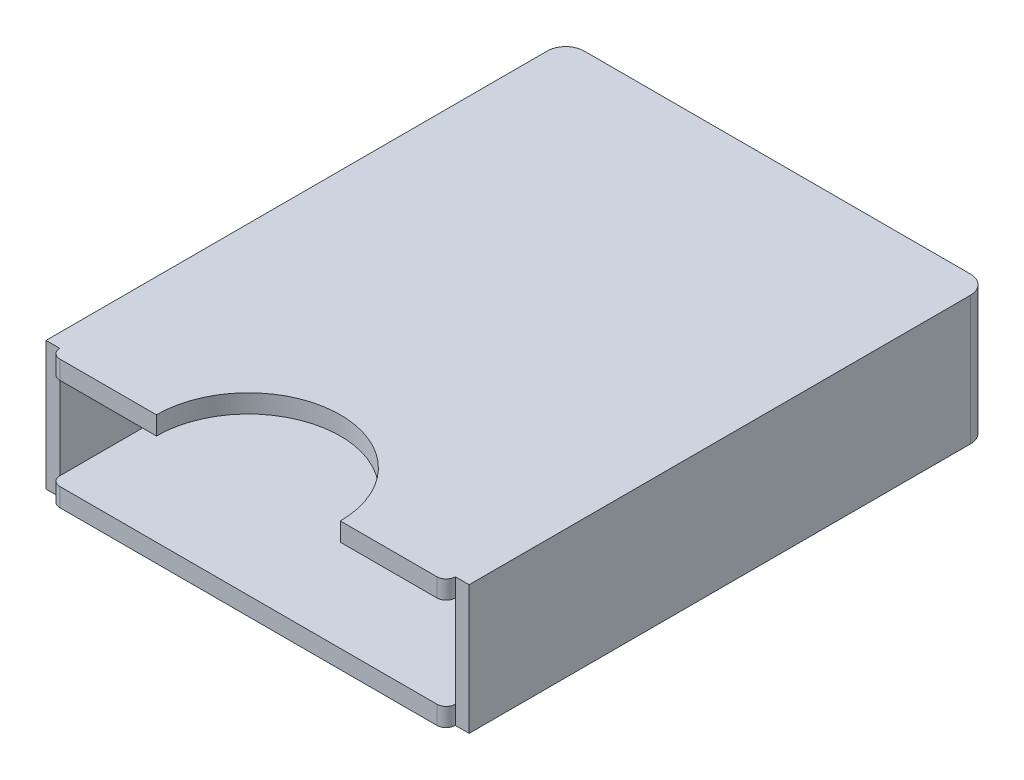
SolidWorks part; units mm, degrees
ref_plane "Front Plane" through (0, 0, 0) normal (0, 0, 1) x (1, 0, 0)
ref_plane "Top Plane" through (0, 0, 0) normal (0, 1, 0) x (1, 0, 0)
ref_plane "Right Plane" through (0, 0, 0) normal (1, 0, 0) x (0, 0, -1)
sketch "Sketch10" plane through (0, 0, 0) normal (0, 1, 0) x (1, 0, 0)
  line L0 (-10.75, -13.5) -> (-11.5, -13.5)
  line L1 (10.5, 14.75) -> (-10.5, 14.75)
  line L2 (11.5, 13.75) -> (11.5, -13.75)
  line L3 (10.5, -14.75) -> (-10.5, -14.75)
  line L4 (-11.5, 13.75) -> (-11.5, -13.75)
  line L5 (4.75, 16.25) -> (-4.75, 16.25)
  line L6 (4.75, 16.25) -> (4.75, 14.75)
  line L7 (10.25, 14) -> (-10.25, 14)
  line L8 (10.75, 13.5) -> (10.75, -13.5)
  line L9 (10.25, -14) -> (-10.25, -14)
  line L10 (-10.75, 13.5) -> (-10.75, -13.5)
  line L11 (4.75, 14.75) -> (-4.75, 14.75)
  line L12 (-4.75, 16.25) -> (-4.75, 14.75)
  line L13 (10.75, -13.5) -> (11.5, -13.5)
  arc A0 (-11.5, -13.75) -> (-10.5, -14.75) centre (-10.5, -13.75) ccw
  arc A1 (11.5, -13.75) -> (10.5, -14.75) centre (10.5, -13.75) cw
  arc A2 (11.5, 13.75) -> (10.5, 14.75) centre (10.5, 13.75) ccw
  arc A3 (-11.5, 13.75) -> (-10.5, 14.75) centre (-10.5, 13.75) cw
  arc A4 (-10.75, 13.5) -> (-10.25, 14) centre (-10.25, 13.5) cw
  arc A5 (-10.75, -13.5) -> (-10.25, -14) centre (-10.25, -13.5) ccw
  arc A6 (10.25, -14) -> (10.75, -13.5) centre (10.25, -13.5) ccw
  arc A7 (10.75, 13.5) -> (10.25, 14) centre (10.25, 13.5) ccw
  point P0 (0, 0)
  point P6 (0, 0)
extrude "Boss-Extrude23" add sketch "Sketch10" along normal blind 1 contours L8 A7 L7 A4 L10 A5 L9 A6 | A3 L4 A0 L3 A1 L2 A2 L1 A7 L8 A6 L9 A5 L10 A4 L7 region at (-11.125, 0, 13.1357) region at (0, 0, 0)
extrude "Boss-Extrude27" add sketch "Sketch10<6>" along normal blind 6 contours A7 L8 L13 L2 A2 L1 A3 L4 L0 L10 A4 L7 region at (-11.125, 0, 13.1357)
sketch "Sketch10<6>" plane through (0, 0, 0) normal (0, 1, 0) x (1, 0, 0) same geometry as "Sketch10"
extrude "Boss-Extrude28" add sketch "Sketch10<7>" along normal blind 1 from offset 6 contours A7 L8 L13 L2 A2 L1 A3 L4 L0 L10 A4 L7 | L8 A7 L7 A4 L10 A5 L9 A6 region at (-11.125, 0, 13.1357) region at (0, 0, 0)
sketch "Sketch10<7>" plane through (0, 0, 0) normal (0, 1, 0) x (1, 0, 0) same geometry as "Sketch10"
sketch "Sketch13" plane through (0, 7, 0) normal (0, 1, 0) x (1, 0, 0)
  line L0 (10.25, -14) -> (-10.25, -14) construction
  line L1 (-5, -14) -> (5, -14)
  arc A0 (5, -14) -> (-5, -14) centre (0, -14) ccw
extrude "Cut-Extrude9" cut sketch "Sketch13" against normal blind 1
sketch "Sketch15" plane through (0, 0, -14.75) normal (0, 0, -1) x (-1, 0, 0)
  line L1 (5, 1) -> (-5, 1)
  line L2 (5, 1) -> (5, 3)
  line L3 (5, 3) -> (-5, 3)
  line L4 (-5, 1) -> (-5, 3)
extrude "Cut-Extrude11" cut sketch "Sketch15" against normal blind 10
